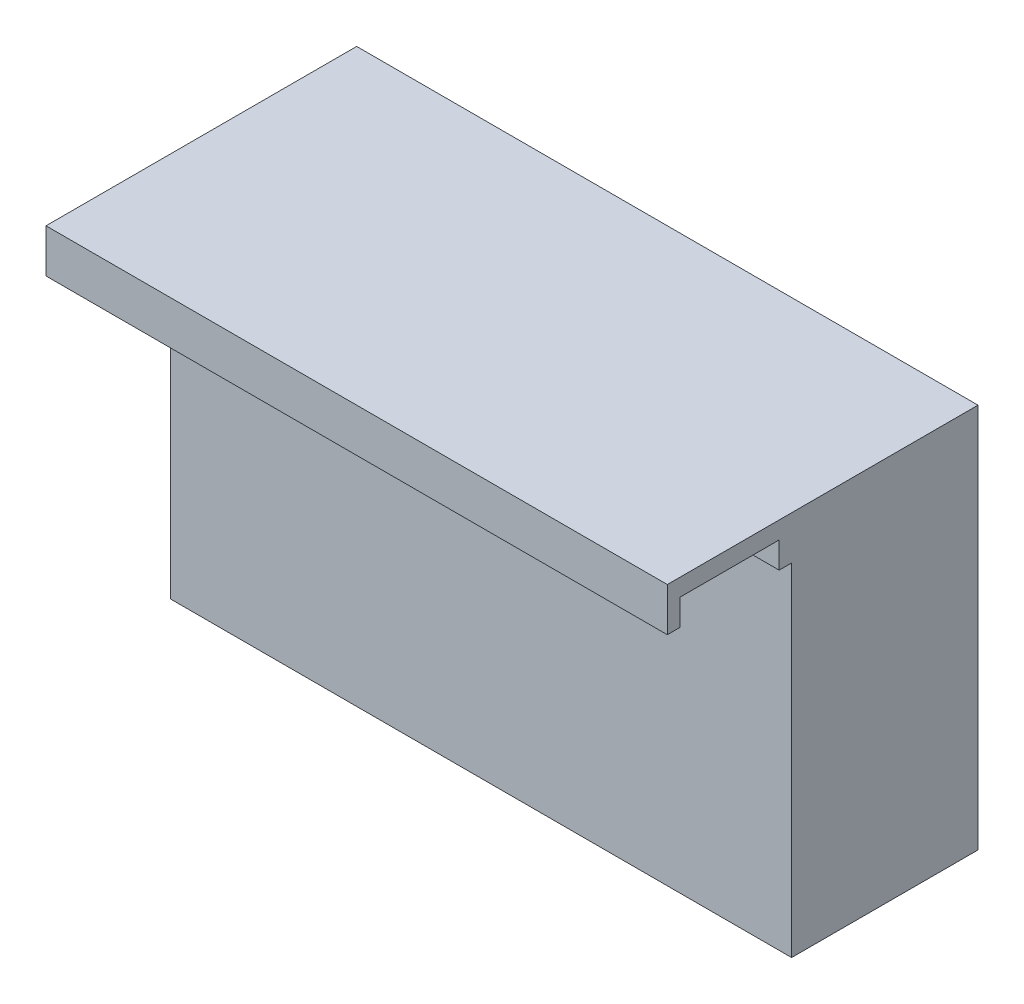
SolidWorks part; units mm, degrees
ref_plane "Front Plane" through (0, 0, 0) normal (0, 0, 1) x (1, 0, 0)
ref_plane "Top Plane" through (0, 0, 0) normal (0, 1, 0) x (1, 0, 0)
ref_plane "Right Plane" through (0, 0, 0) normal (1, 0, 0) x (0, 0, -1)
sketch "Sketch1" plane through (0, 0, 0) normal (0, 1, 0) x (1, 0, 0)
  line L1 (0, 0) -> (-100, 0)
  line L2 (0, 0) -> (0, 20)
  line L3 (0, 20) -> (-100, 20)
  line L4 (-100, 0) -> (-100, 20)
  dimension "D1" = 20
  dimension "D2" = 100
extrude "Boss-Extrude1" add sketch "Sketch1" along normal blind 7
sketch "Sketch2" plane through (-100, 0, 0) normal (-1, 0, 0) x (0, 0, 1)
  line L5 (-20, 0) -> (0, 0) construction
  line L6 (-2, -4.2141) -> (-18, -4.2141)
  line L7 (-2, -4.2141) -> (-2, 4.2141)
  line L8 (-2, 4.2141) -> (-18, 4.2141)
  line L9 (-18, -4.2141) -> (-18, 4.2141)
  line L10 (-2, -4.2141) -> (-18, 4.2141) construction
  line L11 (-2, 4.2141) -> (-18, -4.2141) construction
  point P0 (-10, 0)
  dimension "D1" = 16
extrude "Cut-Extrude1" cut sketch "Sketch2" against normal through all
sketch "Sketch3" plane through (0, 0, -20) normal (0, 0, -1) x (-1, 0, 0)
  line L0 (100, 7) -> (100, 0) construction
  line L1 (0, 7) -> (100, 7)
  line L2 (0, 7) -> (0, -55)
  line L3 (0, -55) -> (100, -55)
  line L4 (100, 7) -> (100, -55)
  dimension "D1" = 62
extrude "Boss-Extrude2" add sketch "Sketch3" along normal blind 30
sketch "Sketch4" plane through (0, 0, -50) normal (0, 0, -1) x (-1, 0, 0)
  line L0 (0, -24) -> (100, -24) construction
  line L1 (0, 7) -> (0, -55) construction
  line L2 (100, -55) -> (100, 7) construction
  line L3 (50, 7) -> (50, -24) construction
  line L4 (100, 7) -> (0, 7) construction
  line L6 (6, -52.25) -> (94, -52.25)
  line L7 (6, -52.25) -> (6, 4.25)
  line L8 (6, 4.25) -> (94, 4.25)
  line L9 (94, -52.25) -> (94, 4.25)
  line L10 (6, -52.25) -> (94, 4.25) construction
  line L11 (6, 4.25) -> (94, -52.25) construction
  dimension "D1" = 88
  dimension "D2" = 56.5
extrude "Cut-Extrude2" cut sketch "Sketch4" against normal blind 27.5
sketch "Sketch5" plane through (-94, 0, 0) normal (1, 0, 0) x (0, 0, -1)
  line L1 (22.5, -27.6063) -> (31.2, -27.6063) construction
  line L2 (22.5, -52.25) -> (22.5, 4.25) construction
  line L3 (38.8863, 2.25) -> (38.8863, 4.25) construction
  line L6 (31.2, 2.25) -> (38.8863, 2.25)
  line L10 (31.2, -50.25) -> (38.8863, -50.25)
  line L12 (22.5, 4.25) -> (50, 4.25) construction
  line L13 (38.8863, -50.25) -> (38.8863, -52.25) construction
  line L14 (22.5, -52.25) -> (50, -52.25) construction
  line L15 (31.2, 2.25) -> (31.2, -50.25)
  line L16 (38.8863, 2.25) -> (38.8863, -50.25)
  dimension "D1" = 8.7
  dimension "D2" = 52.5
extrude "Cut-Extrude3" cut sketch "Sketch5" against normal through all
sketch "Sketch6" plane through (-6, 0, 0) normal (-1, 0, 0) x (0, 0, 1)
  line L0 (-22.5, -24) -> (-50, -24) construction
  line L1 (-22.5, 4.25) -> (-22.5, -52.25) construction
  line L2 (-50, 4.25) -> (-50, -52.25) construction
  line L4 (-50, -17.5) -> (-22.5, -17.5)
  line L5 (-50, -17.5) -> (-50, -30.5)
  line L6 (-50, -30.5) -> (-22.5, -30.5)
  line L7 (-22.5, -17.5) -> (-22.5, -30.5)
  line L8 (-50, -17.5) -> (-22.5, -30.5) construction
  line L9 (-50, -30.5) -> (-22.5, -17.5) construction
  point P6 (-36.25, -24)
  point P11 (-44.5908, -17.5)
  point P12 (-22.5, -17.5)
  dimension "D1" = 13
extrude "Cut-Extrude4" cut sketch "Sketch6" against normal blind 3
sketch "Sketch7" plane through (0, 0, -50) normal (0, 0, -1) x (-1, 0, 0)
  line L0 (6, -52.25) -> (11, -52.25) construction
  line L1 (6, -52.25) -> (94, -52.25) construction
  line L2 (6, -52.25) -> (64, -52.25) construction
  line L3 (6, -52.25) -> (94, -52.25) construction
  line L5 (6, -52.25) -> (64, -52.25)
  line L6 (6, -52.25) -> (6, -54.55)
  line L7 (6, -54.55) -> (64, -54.55)
  line L8 (64, -52.25) -> (64, -54.55)
  dimension "D1" = 5
  dimension "D2" = 58
  dimension "D3" = 2.3
extrude "Cut-Extrude5" cut sketch "Sketch7" against normal blind 23
sketch "Sketch9" plane through (0, -52.25, 0) normal (0, 1, 0) x (1, 0, 0)
  line L0 (-37.9606, 22.5) -> (-37.9606, 38.5) construction
  line L1 (-6, 22.5) -> (-94, 22.5) construction
  line L2 (-64, 27) -> (-64, 50) construction
  line L3 (-37.9606, 38.5) -> (-64, 38.5)
  line L5 (-37.9606, 33.5) -> (-64, 33.5)
  line L6 (-64, 38.5) -> (-64, 33.5)
  line L8 (-37.9606, 38.5) -> (-6.413, 38.5)
  line L10 (-37.9606, 33.5) -> (-6.413, 33.5)
  line L11 (-6.413, 38.5) -> (-6.413, 33.5)
  dimension "D1" = 16
  dimension "D2" = 5
extrude "Cut-Extrude6" cut sketch "Sketch9" against normal blind 23
